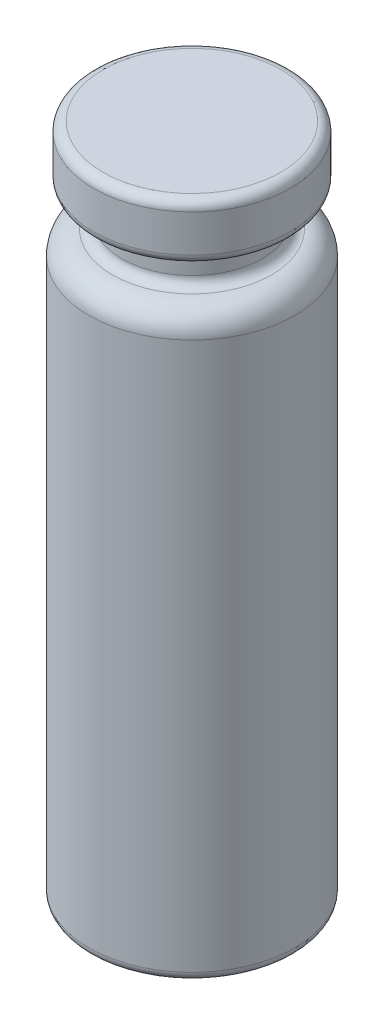
SolidWorks part; units mm, degrees
material "Vidrio"
ref_plane "Alzado" through (0, 0, 0) normal (0, 0, 1) x (1, 0, 0)
ref_plane "Planta" through (0, 0, 0) normal (0, 1, 0) x (1, 0, 0)
ref_plane "Vista lateral" through (0, 0, 0) normal (1, 0, 0) x (0, 0, -1)
sketch "Croquis1" plane through (0, 0, 0) normal (0, 1, 0) x (1, 0, 0)
  circle A0 centre (0, 0) radius 11
  dimension "D1" = 22
extrude "Saliente-Extruir1" add sketch "Croquis1" along normal blind 62
sketch "Croquis2" plane through (0, 62, 0) normal (0, 1, 0) x (1, 0, 0)
  circle A0 centre (0, 0) radius 7.5
  dimension "D1" = 15
extrude "Saliente-Extruir2" add sketch "Croquis2" along normal blind 4
sketch "Croquis3" plane through (0, 66, 0) normal (0, 1, 0) x (1, 0, 0)
  circle A0 centre (0, 0) radius 10.5
  dimension "D1" = 21
extrude "Saliente-Extruir3" add sketch "Croquis3" along normal blind 6
fillet "Redondeo1" radius 2.5 1 edges at (0, 62, 11)
fillet "Redondeo2" radius 1 4 edges at (0, 72, 10.5) (0, 66, 10.5) (0, 66, 7.5) (0, 62, 7.5)
fillet "Redondeo3" radius 1 1 edges at (0, 0, 11)
